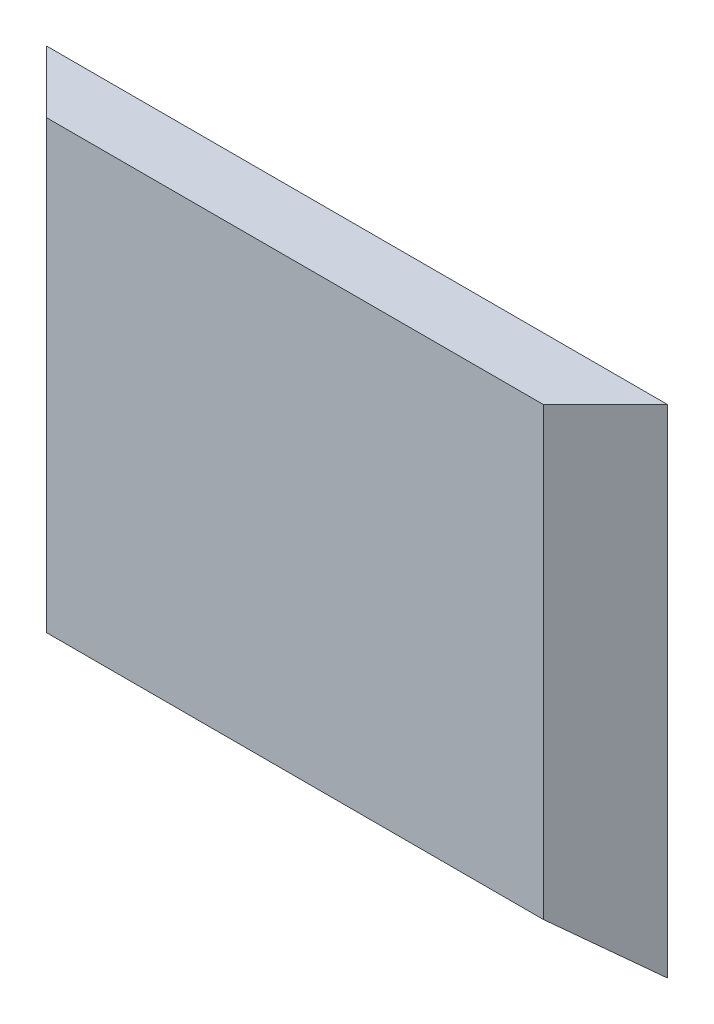
SolidWorks part; units mm, degrees
ref_plane "Front Plane" through (0, 0, 0) normal (0, 0, 1) x (1, 0, 0)
ref_plane "Top Plane" through (0, 0, 0) normal (0, 1, 0) x (1, 0, 0)
ref_plane "Right Plane" through (0, 0, 0) normal (1, 0, 0) x (0, 0, -1)
sketch "Sketch1" plane through (0, 0, 0) normal (0, 0, 1) x (1, 0, 0)
  line L1 (-25, 20) -> (25, 20)
  line L2 (-25, 20) -> (-25, -20)
  line L3 (-25, -20) -> (25, -20)
  line L4 (25, 20) -> (25, -20)
  line L5 (-25, 20) -> (25, -20) construction
  line L6 (-25, -20) -> (25, 20) construction
  point P0 (0, 0)
  dimension "D1" = 40
  dimension "D2" = 50
extrude "Boss-Extrude1" add sketch "Sketch1" along normal blind 5
sketch "Sketch2" plane through (0, 0, 0) normal (0, 1, 0) x (1, 0, 0)
  line L0 (-25, 0) -> (-20, -5)
  line L1 (25, 0) -> (20, -5)
  line L2 (25, 0) -> (-25, 0) construction
  line L3 (-25, -5) -> (-25, 0) construction
  line L4 (-25, -5) -> (-25, 0)
  line L5 (25, -5) -> (-25, -5) construction
  line L6 (25, -5) -> (20, -5)
  line L7 (25, -5) -> (25, 0) construction
  line L8 (25, -5) -> (25, 0)
  line L9 (-20, -5) -> (-25, -5)
  dimension "D1" = 45
  dimension "D2" = 45
extrude "Cut-Extrude1" cut sketch "Sketch2" against normal through all both and the other way through all
sketch "Sketch3" plane through (0, 0, 0) normal (1, 0, 0) x (0, 0, -1)
  line L0 (0, -20) -> (-5, -15.9168)
  line L1 (-5, -20) -> (-5, 20) construction
  line L2 (-5, -20) -> (-5, -15.9168)
  line L3 (0, -20) -> (-5, -20) construction
  line L4 (0, -20) -> (-5, -20)
extrude "Cut-Extrude2" cut sketch "Sketch3" against normal through all both and the other way through all
